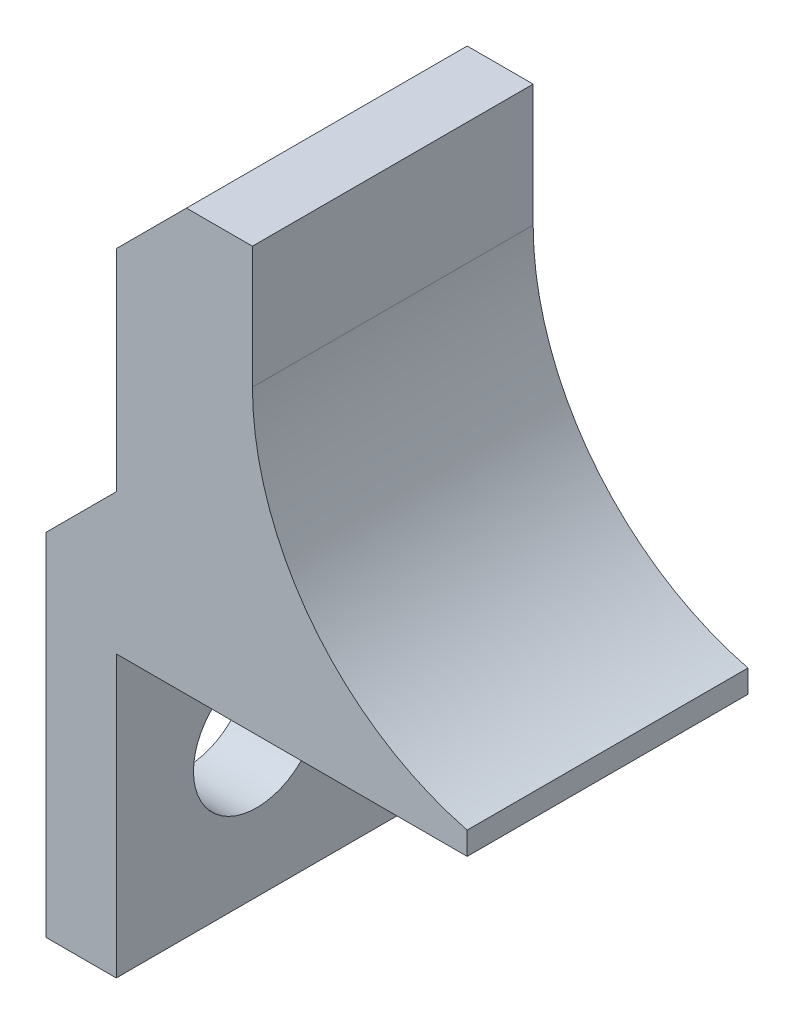
SolidWorks part; units mm, degrees
ref_plane "前视基准面" through (0, 0, 0) normal (0, 0, 1) x (1, 0, 0)
ref_plane "上视基准面" through (0, 0, 0) normal (0, 1, 0) x (1, 0, 0)
ref_plane "右视基准面" through (0, 0, 0) normal (1, 0, 0) x (0, 0, -1)
sketch "草图1" plane through (0, 0, 0) normal (0, 0, 1) x (1, 0, 0)
  line L0 (0, 0) -> (25, 0) construction
  line L1 (0, 5) -> (0, 30)
  line L3 (0, 0) -> (6.25, 0) construction
  line L4 (6.25, 0) -> (6.25, 21.3) construction
  line L5 (6.25, 21.3) -> (9.7, 21.3) construction
  line L6 (6.25, 0) -> (25, 0)
  line L7 (0, 30) -> (9.7, 30)
  line L8 (9.7, 30) -> (9.7, 21.3)
  line L9 (0, 0) -> (6.25, 0)
  line L14 (-5, 5) -> (0, 5)
  line L15 (0, 0) -> (0, -20)
  line L16 (0, -20) -> (-5, -20)
  line L17 (-5, -20) -> (-5, 5)
  line L19 (25, 0) -> (25, 1.6254)
  arc A2 (9.7, 21.3) -> (25, 1.6254) centre (30, 21.3) ccw
  dimension "D2" = 30
  dimension "D3" = 20.3
  dimension "D5" = 21.3
  dimension "D4" = 6.25
  dimension "D6" = 9.7
extrude "凸台-拉伸1" add sketch "草图1" along normal blind 20
sketch "草图3" plane through (-5, 0, 0) normal (-1, 0, 0) x (0, 0, 1)
  line L0 (0, -20) -> (10, -20) construction
  line L1 (20, -20) -> (0, -20) construction
  line L2 (10, -20) -> (10, -10) construction
  circle A0 centre (10, -10) radius 4.5
extrude "切除-拉伸2" cut sketch "草图3" against normal blind 20
chamfer "倒角1" distance 5 angle 45 1 edges at (0, 5, 10)
chamfer "倒角2" distance 5 angle 45 1 edges at (0, 30, 10)
